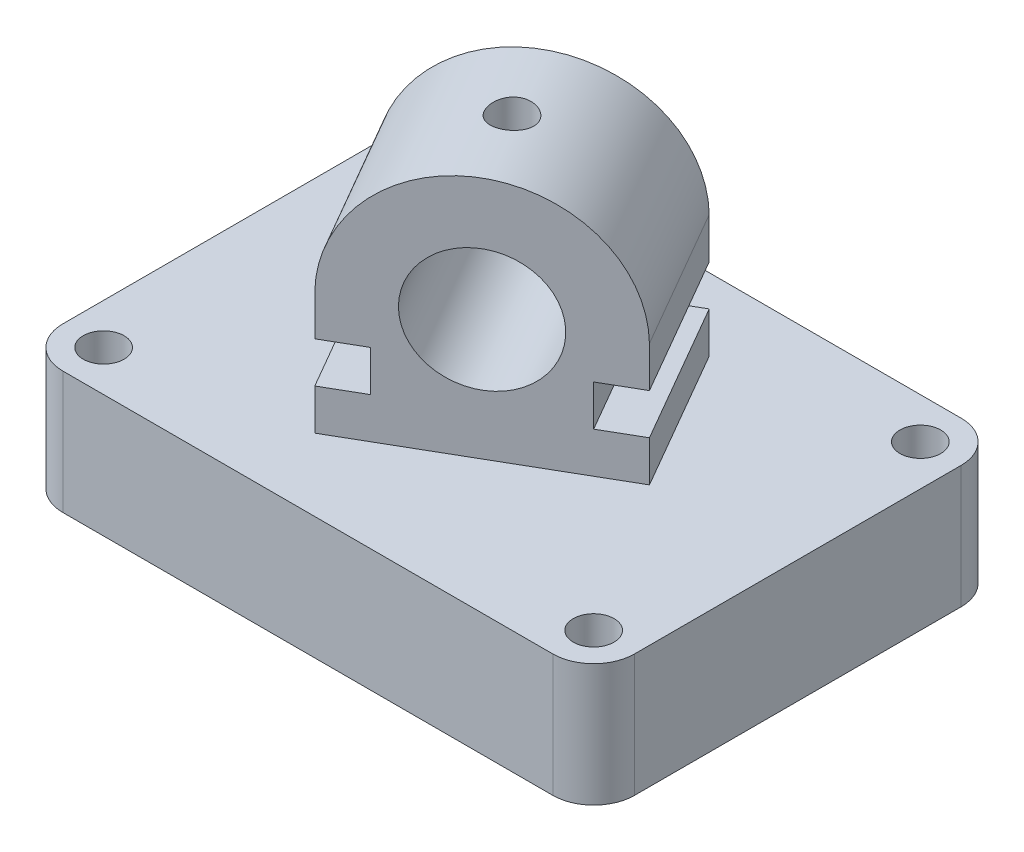
SolidWorks part; units mm, degrees
ref_plane "Front Plane" through (0, 0, 0) normal (0, 0, 1) x (1, 0, 0)
ref_plane "Top Plane" through (0, 0, 0) normal (0, 1, 0) x (1, 0, 0)
ref_plane "Right Plane" through (0, 0, 0) normal (1, 0, 0) x (0, 0, -1)
sketch "Sketch1" plane through (0, 0, 0) normal (0, 1, 0) x (1, 0, 0)
  line L1 (-38.1, 31.75) -> (38.1, 31.75)
  line L2 (-44.45, 25.4) -> (-44.45, -25.4)
  line L3 (-38.1, -31.75) -> (38.1, -31.75)
  line L4 (44.45, 25.4) -> (44.45, -25.4)
  line L5 (-44.45, 31.75) -> (44.45, -31.75) construction
  line L6 (-44.45, -31.75) -> (44.45, 31.75) construction
  arc A0 (38.1, 31.75) -> (44.45, 25.4) centre (38.1, 25.4) cw
  arc A1 (38.1, -31.75) -> (44.45, -25.4) centre (38.1, -25.4) ccw
  arc A2 (-44.45, -25.4) -> (-38.1, -31.75) centre (-38.1, -25.4) ccw
  arc A3 (-38.1, 31.75) -> (-44.45, 25.4) centre (-38.1, 25.4) ccw
  circle A4 centre (-38.1, 25.4) radius 3.175
  circle A5 centre (-38.1, -25.4) radius 3.175
  circle A6 centre (38.1, -25.4) radius 3.175
  circle A7 centre (38.1, 25.4) radius 3.175
  point P0 (0, 0)
  dimension "D1" = 6.35
  dimension "D4" = 6.35
  dimension "D2" = 76.2
  dimension "D3" = 50.8
extrude "Boss-Extrude1" add sketch "Sketch1" along normal blind 19.05
ref_axis "Axis1" through (0, 0, 0) along (0, 1, 0)
ref_plane "Plane1" through (0, 0, 0) normal (-0.5, 0, -0.866) x (0, 1, 0)
sketch "Sketch3" plane through (0, 0, 0) normal (-0.5, 0, -0.866) x (0, 1, 0)
  line L0 (0, 0) -> (19.05, 0) construction
  line L1 (19.05, 19.0483) -> (25.4, 19.0483)
  line L2 (31.75, -19.0483) -> (31.75, -12.6983)
  line L3 (25.4, 12.6983) -> (31.75, 12.6983)
  line L4 (0, 17.1206) -> (0, -48.8706)
  line L5 (19.05, 17.1206) -> (0, 17.1206)
  line L6 (19.05, -48.8706) -> (19.05, 17.1206)
  line L7 (0, -48.8706) -> (19.05, -48.8706)
  line L8 (0, 17.1206) -> (0, -48.8706)
  line L9 (19.05, 17.1206) -> (0, 17.1206)
  line L10 (19.05, -48.8706) -> (19.05, 19.0483)
  line L11 (0, -48.8706) -> (19.05, -48.8706)
  line L12 (31.75, 12.6983) -> (31.75, 19.0483)
  line L13 (25.4, 12.6983) -> (25.4, 19.0483)
  line L14 (25.4, -12.6983) -> (31.75, -12.6983)
  line L15 (25.4, -12.6983) -> (25.4, -19.0483)
  line L16 (25.4, -19.0483) -> (19.05, -19.0483)
  line L17 (31.75, 19.0483) -> (38.1, 19.0483)
  line L18 (31.75, -19.0483) -> (38.1, -19.0483)
  line L19 (19.05, -19.0483) -> (19.05, 19.0483)
  line L20 (19.05, -48.8706) -> (19.05, 17.1206) construction
  line L21 (19.05, 48.8706) -> (19.05, -17.1206) construction
  line L22 (19.05, 25.7948) -> (19.05, 51.1948) construction
  line L23 (0, 25.7948) -> (0, 51.1948) construction
  arc A0 (38.1, 19.0483) -> (38.1, -19.0483) centre (37.8442, 0) cw
  circle A1 centre (37.8442, 0) radius 9.525
  dimension "D2" = 19.05
  dimension "D11" = 19.05
  dimension "D3" = 6.35
  dimension "D4" = 6.35
  dimension "D5" = 6.35
  dimension "D6" = 6.35
  dimension "D7" = 6.35
  dimension "D8" = 6.35
  dimension "D9" = 6.35
  dimension "D10" = 6.35
  dimension "D1" = 0
extrude "Boss-Extrude2" add sketch "Sketch3" along normal mid plane 25.4 contours A0 L17 L12 L3 L13 L1 L10 L19 L16 L15 L14 L2 L18 A1 region at (16.0313, 22.225, -9.2556)
ref_plane "Plane2" through (0, 38.1, 0) normal (0, 1, 0) x (1, 0, 0)
sketch "Sketch4" plane through (0, 38.1, 0) normal (0, 1, 0) x (1, 0, 0)
  circle A0 centre (0, 0) radius 3.175
  dimension "D1" = 6.35
extrude "Cut-Extrude1" cut sketch "Sketch4" along normal through all
ref_plane "Plane3" through (0, 19.05, 0) normal (0, 1, 0) x (1, 0, 0)
